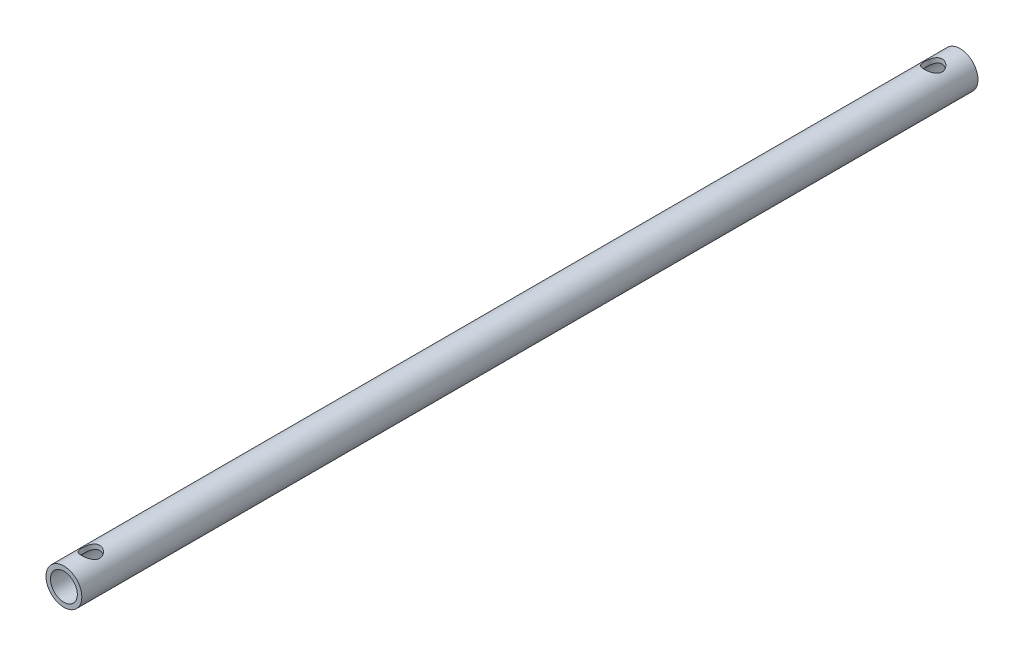
SolidWorks part; units mm, degrees
ref_plane "Plan de face" through (0, 0, 0) normal (0, 0, 1) x (1, 0, 0)
ref_plane "Plan de dessus" through (0, 0, 0) normal (0, 1, 0) x (1, 0, 0)
ref_plane "Plan de droite" through (0, 0, 0) normal (1, 0, 0) x (0, 0, -1)
sketch "Esquisse1" plane through (0, 0, 0) normal (0, 0, 1) x (1, 0, 0)
  circle A0 centre (-4.9182, 1.1045) radius 2
  circle A1 centre (-4.9182, 1.1045) radius 1.5
  dimension "D1" = 3
  dimension "D2" = 4
extrude "Boss.-Extru.1" add sketch "Esquisse1" along normal blind 100
ref_plane "Plan1" through (0, 3.1045, 0) normal (0, 1, 0) x (1, 0, 0)
sketch "Esquisse2" plane through (0, 3.1045, 0) normal (0, 1, 0) x (1, 0, 0)
  line L0 (-4.9182, 0) -> (-4.9182, -100) construction
  line L1 (-2.9182, 0) -> (-6.9182, 0) construction
  line L2 (-6.9182, -100) -> (-2.9182, -100) construction
  circle A0 centre (-4.9182, -3) radius 1
  circle A1 centre (-4.9182, -97) radius 1
  dimension "D2" = 2
  dimension "D3" = 2
  dimension "D1" = 3
  dimension "D4" = 3
extrude "Enlèv. mat.-Extru.1" cut sketch "Esquisse2" against normal through all
